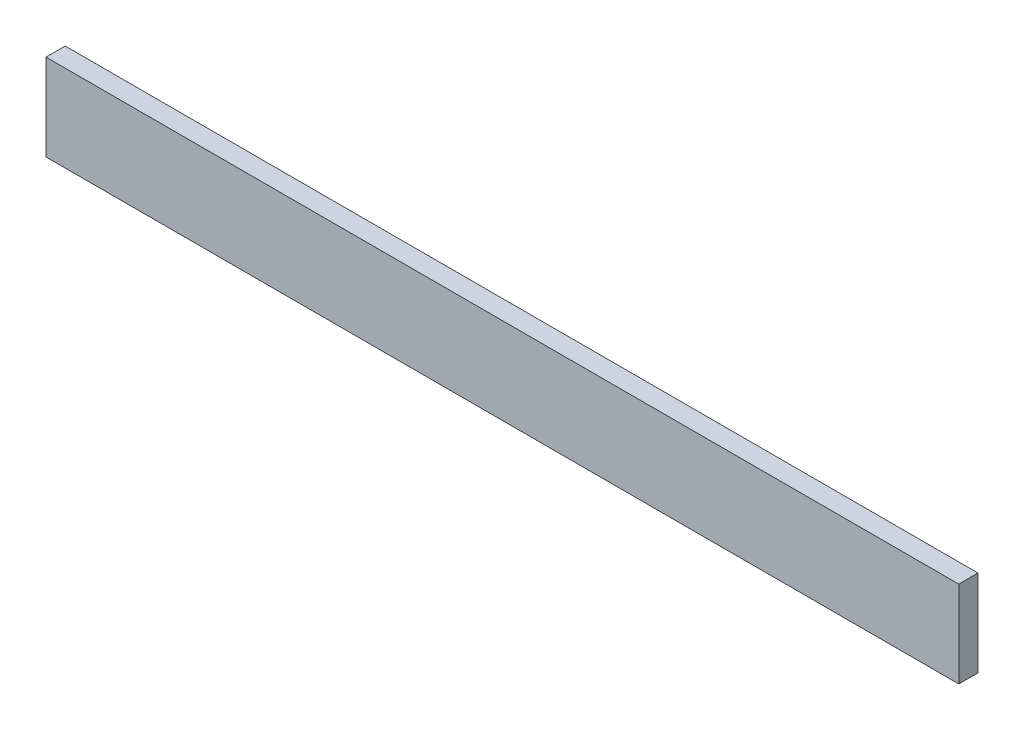
SolidWorks part; units mm, degrees
ref_plane "Front Plane" through (0, 0, 0) normal (0, 0, 1) x (1, 0, 0)
ref_plane "Top Plane" through (0, 0, 0) normal (0, 1, 0) x (1, 0, 0)
ref_plane "Right Plane" through (0, 0, 0) normal (1, 0, 0) x (0, 0, -1)
sketch "Sketch1" plane through (0, 0, 0) normal (0, 0, 1) x (1, 0, 0)
  line L1 (-795.3333, 45) -> (154.6667, 45)
  line L2 (-795.3333, 45) -> (-795.3333, -45)
  line L3 (-795.3333, -45) -> (154.6667, -45)
  line L4 (154.6667, 45) -> (154.6667, -45)
  point P0 (0, 0)
  dimension "D1" = 90
  dimension "D2" = 950
extrude "Boss-Extrude1" add sketch "Sketch1" along normal blind 10 and the other way blind 10
